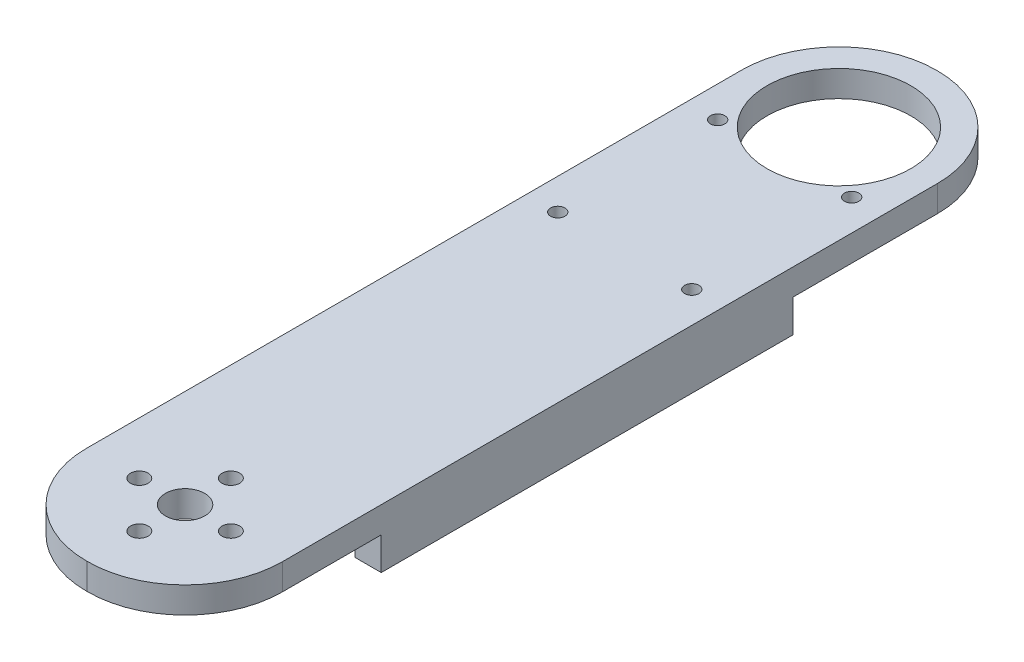
SolidWorks part; units mm, degrees
ref_plane "Front Plane" through (0, 0, 0) normal (0, 0, 1) x (1, 0, 0)
ref_plane "Top Plane" through (0, 0, 0) normal (0, 1, 0) x (1, 0, 0)
ref_plane "Right Plane" through (0, 0, 0) normal (1, 0, 0) x (0, 0, -1)
ref_plane "PY_m20_000" through (0, -20, 0) normal (0, 1, 0) x (1, 0, 0)
sketch "S_prism1" plane through (0, -20, 0) normal (0, 1, 0) x (1, 0, 0)
  line L0 (-0.1, -15) -> (0.1, -15)
  line L1 (15, -0.1) -> (15, 100.1)
  line L2 (0.1, 115) -> (-0.1, 115)
  line L3 (-15, 100.1) -> (-15, -0.1)
  arc A0 (-15, -0.1) -> (-0.1, -15) centre (-0.1, -0.1) ccw
  arc A1 (0.1, -15) -> (15, -0.1) centre (0.1, -0.1) ccw
  arc A2 (15, 100.1) -> (0.1, 115) centre (0.1, 100.1) ccw
  arc A3 (-0.1, 115) -> (-15, 100.1) centre (-0.1, 100.1) ccw
extrude "Boss_1" add sketch "S_prism1" along normal blind 4
ref_plane "PZ_m78_000" through (0, 0, -78) normal (0, 0, 1) x (1, 0, 0)
sketch "S_box2" plane through (0, 0, -78) normal (0, 0, 1) x (1, 0, 0)
  line L0 (-15, -25) -> (-11, -25)
  line L1 (-11, -25) -> (-11, -19.5)
  line L2 (-11, -19.5) -> (-15, -19.5)
  line L3 (-15, -19.5) -> (-15, -25)
  dimension "P1" = 15
  dimension "P2" = 25
  dimension "P3" = 11
  dimension "P4" = 25
  dimension "P5" = 11
  dimension "P6" = 19.5
  dimension "P7" = 15
  dimension "P8" = 19.5
extrude "Boss_2" add sketch "S_box2" along normal blind 63
sketch "S_box3" plane through (0, 0, -78) normal (0, 0, 1) x (1, 0, 0)
  line L0 (11, -25) -> (15, -25)
  line L1 (15, -25) -> (15, -19.5)
  line L2 (15, -19.5) -> (11, -19.5)
  line L3 (11, -19.5) -> (11, -25)
  dimension "P1" = 11
  dimension "P2" = 25
  dimension "P3" = 15
  dimension "P4" = 25
  dimension "P5" = 15
  dimension "P6" = 19.5
  dimension "P7" = 11
  dimension "P8" = 19.5
extrude "Boss_3" add sketch "S_box3" along normal blind 63
ref_plane "PY_m20_100" through (0, -20.1, 0) normal (0, 1, 0) x (1, 0, 0)
sketch "S_hole4" plane through (0, -20.1, 0) normal (0, 1, 0) x (1, 0, 0)
  circle A0 centre (0, 0) radius 3
  dimension "D1_S_hole4" = 6
extrude "Hole_4" cut sketch "S_hole4" along normal blind 4.2
sketch "S_hole5" plane through (0, -20.1, 0) normal (0, 1, 0) x (1, 0, 0)
  circle A0 centre (7, 0) radius 1.35
  dimension "D1_S_hole5" = 2.7
  dimension "P2" = 7
extrude "Hole_5" cut sketch "S_hole5" along normal blind 4.2
sketch "S_hole6" plane through (0, -20.1, 0) normal (0, 1, 0) x (1, 0, 0)
  circle A0 centre (0, -7) radius 1.35
  dimension "D1_S_hole6" = 2.7
  dimension "P2" = 7
extrude "Hole_6" cut sketch "S_hole6" along normal blind 4.2
sketch "S_hole7" plane through (0, -20.1, 0) normal (0, 1, 0) x (1, 0, 0)
  circle A0 centre (-7, 0) radius 1.35
  dimension "D1_S_hole7" = 2.7
  dimension "P2" = 7
extrude "Hole_7" cut sketch "S_hole7" along normal blind 4.2
sketch "S_hole8" plane through (0, -20.1, 0) normal (0, 1, 0) x (1, 0, 0)
  circle A0 centre (0, 7) radius 1.35
  dimension "D1_S_hole8" = 2.7
  dimension "P2" = 7
extrude "Hole_8" cut sketch "S_hole8" along normal blind 4.2
sketch "S_hole9" plane through (0, -20.1, 0) normal (0, 1, 0) x (1, 0, 0)
  circle A0 centre (0, 100) radius 11
  dimension "D1_S_hole9" = 22
  dimension "P2" = 100
extrude "Hole_9" cut sketch "S_hole9" along normal blind 4.2
sketch "S_hole10" plane through (0, -20.1, 0) normal (0, 1, 0) x (1, 0, 0)
  circle A0 centre (-10.25, 91.7) radius 1.1
  dimension "D1_S_hole10" = 2.2
  dimension "P2" = 10.25
  dimension "P3" = 91.7
extrude "Hole_10" cut sketch "S_hole10" along normal blind 4.2
sketch "S_hole11" plane through (0, -20.1, 0) normal (0, 1, 0) x (1, 0, 0)
  circle A0 centre (10.25, 91.7) radius 1.1
  dimension "D1_S_hole11" = 2.2
  dimension "P2" = 10.25
  dimension "P3" = 91.7
extrude "Hole_11" cut sketch "S_hole11" along normal blind 4.2
sketch "S_hole12" plane through (0, -20.1, 0) normal (0, 1, 0) x (1, 0, 0)
  circle A0 centre (-10.25, 67.25) radius 1.1
  dimension "D1_S_hole12" = 2.2
  dimension "P2" = 10.25
  dimension "P3" = 67.25
extrude "Hole_12" cut sketch "S_hole12" along normal blind 4.2
sketch "S_hole13" plane through (0, -20.1, 0) normal (0, 1, 0) x (1, 0, 0)
  circle A0 centre (10.25, 67.25) radius 1.1
  dimension "D1_S_hole13" = 2.2
  dimension "P2" = 10.25
  dimension "P3" = 67.25
extrude "Hole_13" cut sketch "S_hole13" along normal blind 4.2
equation "\"plate_t\" = 3"
equation "\"clearance\" = 0.4"
